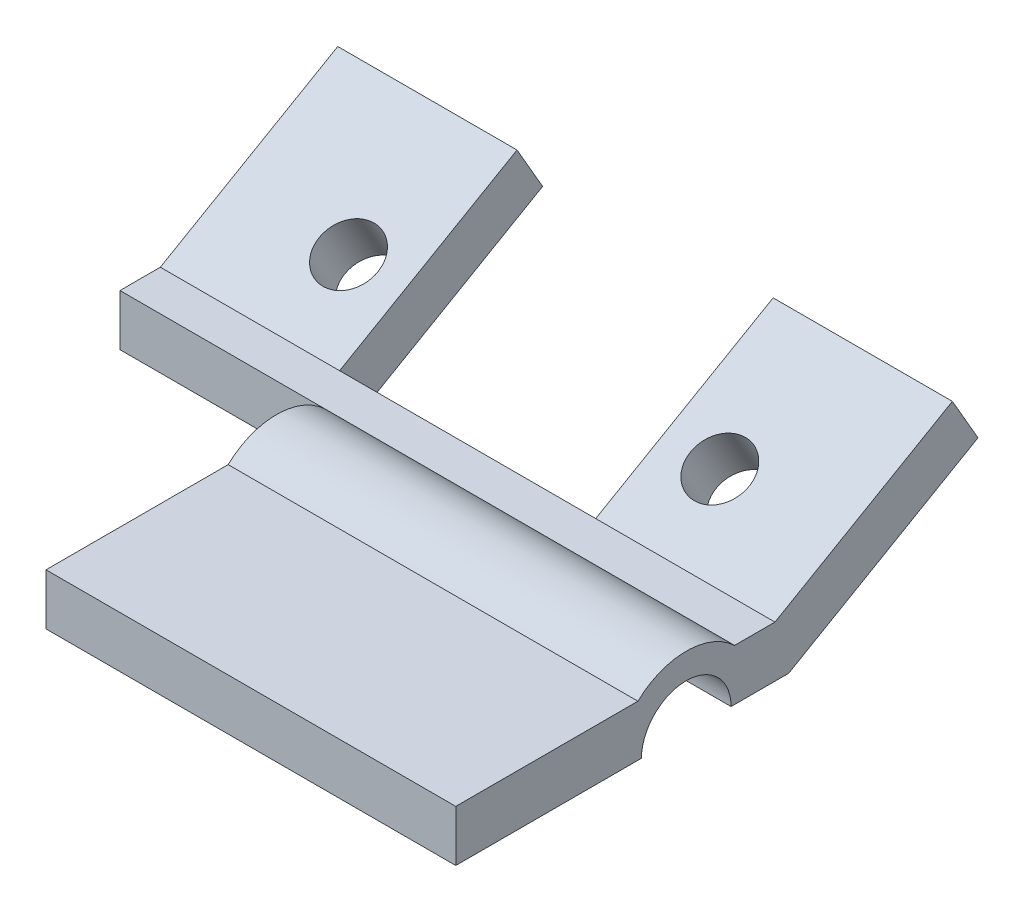
SolidWorks part; units mm, degrees
ref_plane "Front Plane" through (0, 0, 0) normal (0, 0, 1) x (1, 0, 0)
ref_plane "Top Plane" through (0, 0, 0) normal (0, 1, 0) x (1, 0, 0)
ref_plane "Right Plane" through (0, 0, 0) normal (1, 0, 0) x (0, 0, -1)
sketch "Sketch1" plane through (0, 0, 0) normal (1, 0, 0) x (0, 0, -1)
  line L0 (0, 0) -> (13, 0)
  line L1 (13, 0) -> (20.3923, 4.2679)
  line L2 (20.3923, 4.2679) -> (19.3923, 6)
  line L3 (19.3923, 6) -> (12.4641, 2)
  line L4 (12.4641, 2) -> (0, 2)
  line L5 (0, 2) -> (0, 0)
  circle A0 centre (9, 0) radius 1.75
  circle A1 centre (9, 0) radius 2.75
  dimension "D2" = 3.5
  dimension "D3" = 1
  dimension "D1" = 2
  dimension "D4" = 13
  dimension "D5" = 30
  dimension "D6" = 8
  dimension "D7" = 4
extrude "Boss-Extrude1" add sketch "Sketch1" along normal blind 24 contours A1 L4 L5 L0 | L0 A1 L4 A0 | L4 A1 | A1 L0 L1 L2 L3 L4 region at (0, 1.8085, -9) region at (0, 2.7921, -15.7621) region at (0, 2.3038, -9) region at (0, 1.0212, -3.2631)
sketch "Sketch2" plane through (0, 2, 0) normal (0, 1, 0) x (1, 0, 0)
  line L0 (24, 10.8875) -> (0, 10.8875) construction
  line L1 (0, 0) -> (8, 0)
  line L2 (0, 0) -> (0, 10.8875)
  line L3 (0, 10.8875) -> (8, 10.8875)
  line L4 (8, 0) -> (8, 10.8875)
  line L5 (24, 7.1125) -> (24, 0) construction
  dimension "D1" = 16
extrude "Cut-Extrude1" cut sketch "Sketch2" against normal through all both and the other way through all
sketch "Sketch3" plane through (0, -3.8971, -2.25) normal (0, 0.866, 0.5) x (1, 0, 0)
  line L0 (0, 14.7942) -> (24, 14.7942) construction
  line L1 (0, 19.7942) -> (0, 11.7942) construction
  line L2 (24, 19.7942) -> (24, 11.7942) construction
  line L3 (4.75, 14.7942) -> (12, 19.7942) construction
  line L4 (24, 19.7942) -> (0, 19.7942) construction
  line L5 (12, 19.7942) -> (19.25, 14.7942) construction
  circle A0 centre (4.75, 14.7942) radius 1.15
  circle A1 centre (19.25, 14.7942) radius 1.15
  dimension "D1" = 2.3
  dimension "D2" = 14.5
  dimension "D3" = 5
extrude "Cut-Extrude2" cut sketch "Sketch3" against normal through all
sketch "Sketch4" plane through (0, -3.8971, -2.25) normal (0, 0.866, 0.5) x (1, 0, 0)
  line L0 (24, 19.7942) -> (0, 19.7942) construction
  line L1 (17, 27.7942) -> (7, 27.7942)
  line L2 (17, 27.7942) -> (17, 11.7942)
  line L3 (17, 11.7942) -> (7, 11.7942)
  line L4 (7, 27.7942) -> (7, 11.7942)
  line L5 (17, 27.7942) -> (7, 11.7942) construction
  line L6 (17, 11.7942) -> (7, 27.7942) construction
  line L7 (24, 11.7942) -> (0, 11.7942) construction
  point P0 (12, 19.7942)
  dimension "D1" = 10
extrude "Cut-Extrude3" cut sketch "Sketch4" against normal blind 20
